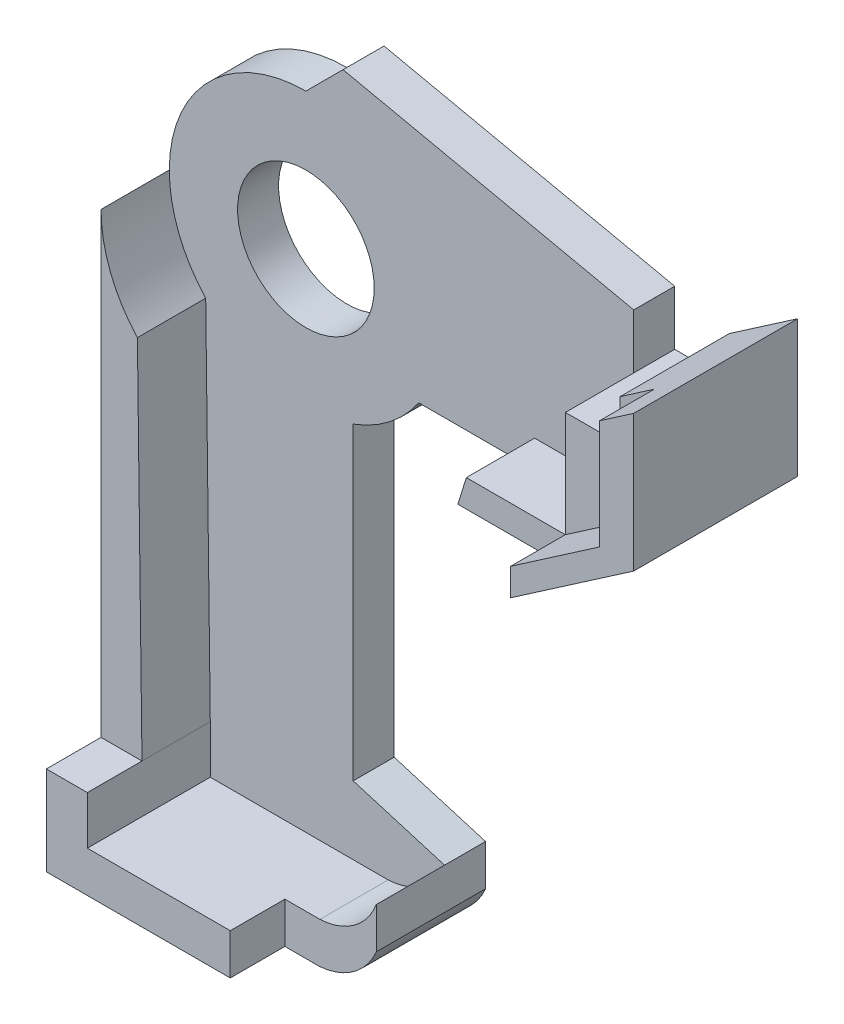
SolidWorks part; units mm, degrees
ref_plane "정면" through (0, 0, 0) normal (0, 0, 1) x (1, 0, 0)
ref_plane "윗면" through (0, 0, 0) normal (0, 1, 0) x (1, 0, 0)
ref_plane "우측면" through (0, 0, 0) normal (1, 0, 0) x (0, 0, -1)
sketch "스케치1" plane through (0, 0, 0) normal (0, 0, 1) x (1, 0, 0)
  line L0 (-5, 0) -> (-5, -20)
  line L1 (-5, -20) -> (3.0125, -20)
  line L2 (5.0758, -18.5) -> (5.0758, -17)
  line L3 (5.0758, -17) -> (1.7308, -16)
  line L4 (1.7308, -16) -> (1.7308, -4.6909)
  line L5 (0, 5) -> (1.3603, 6.3603)
  line L6 (1.3603, 6.3603) -> (12, 4.0646)
  line L7 (12, 4.0646) -> (12, 2.0646)
  line L8 (12, 2.0646) -> (14, 2.0646)
  line L9 (14, 2.0646) -> (14, 3.5646)
  line L10 (14, 3.5646) -> (16.5, 5.2849)
  line L11 (16.5, 5.2849) -> (16.5, 0.2849)
  line L12 (16.5, 0.2849) -> (11.9952, -2.815)
  line L13 (11.9952, -2.815) -> (4.1323, -2.815)
  line L14 (1.7308, -20) -> (1.7308, -18.5)
  line L15 (1.7308, -18.5) -> (-3.5, -18.5)
  line L16 (-3.5, -18.5) -> (-3.5, -16.737)
  line L17 (-3.5, -16.737) -> (-5, -16.737)
  line L18 (15.25, 4.4248) -> (15.25, 0.4248)
  line L19 (15.25, 0.4248) -> (11.9952, -1.815)
  line L20 (11.9952, -1.815) -> (11.9952, -2.815)
  line L21 (12, 2.0646) -> (11.9952, -1.815)
  line L22 (12, 2.0646) -> (11.9952, -1.815)
  line L23 (11.9952, -1.815) -> (8.3726, -1.815)
  line L24 (-3.5, -16.737) -> (-3.6677, -3.3982)
  line L25 (1.7308, -18.5) -> (3.0125, -18.5)
  line L26 (8.3726, -1.815) -> (8.0637, -2.815)
  circle A0 centre (0, 0) radius 2.5
  circle A1 centre (0, 0) radius 5
  arc A2 (5.0758, -17) -> (3.0125, -18.5) centre (2.9037, -16.1814) cw
  arc A3 (5.0758, -18.5) -> (3.0125, -20) centre (2.7998, -17.5384) cw
  dimension "D1" = 5
  dimension "D2" = 10
  dimension "D3" = 20
  dimension "D4" = 4
  dimension "D5" = 1.5
  dimension "D6" = 1.5
  dimension "D7" = 5
  dimension "D8" = 2
  dimension "D9" = 2
  dimension "D10" = 1.5
  dimension "D11" = 16.5
  dimension "D12" = 2.5
  dimension "D13" = 1
extrude "보스-돌출1" add sketch "스케치1" along normal blind 6 contours L19 L20 L12 L11 L10 L18 | L16 L17 L0 L1 L14 L15 region at (-2.1775, -18.9114, 0) region at (13.6751, -0.7715, 0)
extrude "보스-돌출2" add sketch "스케치1<3>" along normal blind 4 contours A1 L0 L17 L24 | A3 L2 A2 L25 L14 L1 | L8 L21 L19 L18 L10 L9 | L23 L26 L13 L20 region at (-4.3135, -9.6667, 0) region at (3.3953, -18.98, 0) region at (13.6725, 1.1252, 0) region at (10.1056, -2.3219, 0)
sketch "스케치1<3>" plane through (0, 0, 0) normal (0, 0, 1) x (1, 0, 0) same geometry as "스케치1"
extrude "보스-돌출3" add sketch "스케치1<4>" along normal blind 1.5 contours A1 A0 | A1 L13 L26 L23 L21 L7 L6 L5 | A2 L3 L4 A1 L24 L16 L15 L25 region at (-3.4355, 3.4355, 0) region at (7.3942, 1.7701, 0) region at (-0.6627, -11.9529, 0)
sketch "스케치1<4>" plane through (0, 0, 0) normal (0, 0, 1) x (1, 0, 0) same geometry as "스케치1"
